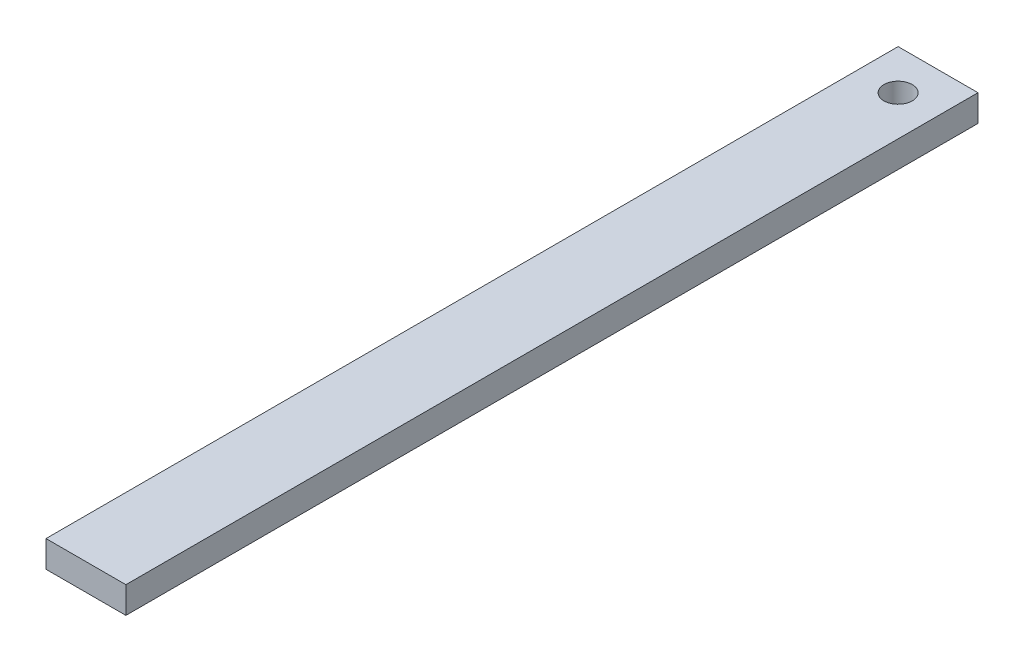
SolidWorks part; units mm, degrees
material "AISI 304"
ref_plane "Front" through (0, 0, 0) normal (0, 0, 1) x (1, 0, 0)
ref_plane "Top" through (0, 0, 0) normal (0, 1, 0) x (1, 0, 0)
ref_plane "Right" through (0, 0, 0) normal (1, 0, 0) x (0, 0, -1)
sketch "Sketch1" plane through (0, 0, 0) normal (0, 0, 1) x (1, 0, 0)
  line L1 (-9.525, -3.175) -> (9.525, -3.175)
  line L2 (-9.525, -3.175) -> (-9.525, 3.175)
  line L3 (-9.525, 3.175) -> (9.525, 3.175)
  line L4 (9.525, -3.175) -> (9.525, 3.175)
  line L5 (-9.525, -3.175) -> (9.525, 3.175) construction
  line L6 (-9.525, 3.175) -> (9.525, -3.175) construction
  point P0 (0, 0)
  dimension "D1" = 6.35
  dimension "D2" = 19.05
extrude "Boss-Extrude1" add sketch "Sketch1" along normal blind 203.2
sketch "Sketch2" plane through (0, 3.175, 0) normal (0, 1, 0) x (1, 0, 0)
  line L0 (0, 0) -> (0, -9.525) construction
  line L1 (9.525, 0) -> (-9.525, 0) construction
  line L2 (0, -9.525) -> (0, -25.4) construction
  line L3 (-4.7625, -203.2) -> (-4.7625, -196.85) construction
  line L4 (9.525, -203.2) -> (-9.525, -203.2) construction
  line L5 (-4.7625, -196.85) -> (-9.525, -196.85) construction
  line L6 (-9.525, -203.2) -> (-9.525, 0) construction
  dimension "D1" = 15.875
  dimension "D2" = 9.525
  dimension "D3" = 6.35
  dimension "D4" = 4.7625
hole_wizard "1/4 Clearance Hole1" positions "Sketch4" profile "Sketch3" hole size "1/4" standard "ANSI Inch" end condition through all
sketch "Sketch4" plane through (0, 3.175, 0) normal (0, 1, 0) x (1, 0, 0)
  point P3 (0, -9.525)
sketch "Sketch3" plane through (0, 3.175, 9.525) normal (1, 0, 0) x (0, 0, 1)
  line L0 (0, 0) -> (0, 6.35)
  line L1 (0, 6.35) -> (3.3782, 6.35)
  line L2 (3.3782, 6.35) -> (3.3782, 0)
  line L5 (3.3782, 0) -> (0, 0)
  line L11 (0, -6.35) -> (0, 107.95) construction
  dimension "Thru Hole Dia." = 6.7564
  dimension "Thru Hole Depth" = 6.35
